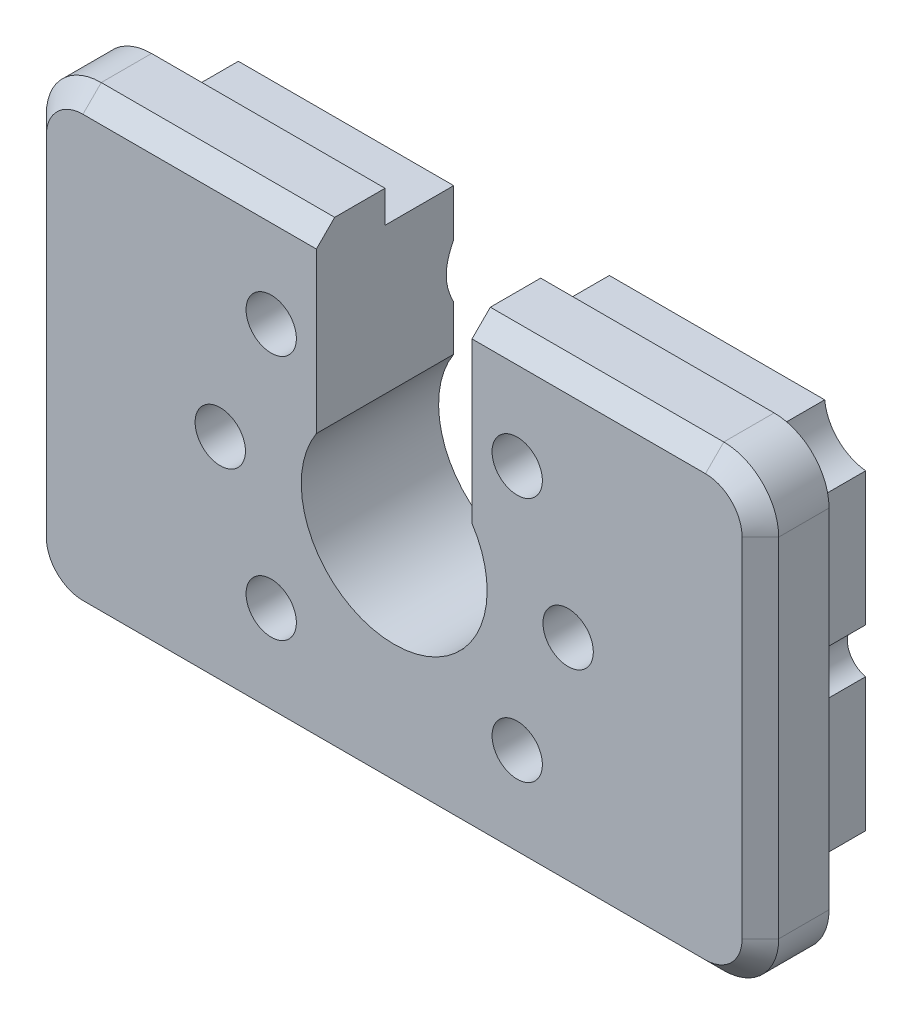
SolidWorks part; units mm, degrees
material "PET"
ref_plane "Front Plane" through (0, 0, 0) normal (0, 0, 1) x (1, 0, 0)
ref_plane "Top Plane" through (0, 0, 0) normal (0, 1, 0) x (1, 0, 0)
ref_plane "Right Plane" through (0, 0, 0) normal (1, 0, 0) x (0, 0, -1)
sketch "Sketch1" plane through (0, 0, 0) normal (0, 0, 1) x (1, 0, 0)
  line L1 (40, -25) -> (-40, -25)
  line L2 (40, -25) -> (40, 25)
  line L3 (40, 25) -> (-40, 25)
  line L4 (-40, -25) -> (-40, 25)
  line L5 (40, -25) -> (-40, 25) construction
  line L6 (40, 25) -> (-40, -25) construction
  point P0 (0, 0)
  dimension "D1" = 50
  dimension "D2" = 80
extrude "Boss-Extrude1" add sketch "Sketch1" against normal blind 7.5
sketch "Sketch2" plane through (0, 0, -7.5) normal (0, 0, -1) x (-1, 0, 0)
  line L8 (36.5, -21.5) -> (36.5, 21.5)
  line L9 (36.5, 21.5) -> (-36.5, 21.5)
  line L10 (-36.5, 21.5) -> (-36.5, -21.5)
  line L11 (-36.5, -21.5) -> (36.5, -21.5)
  line L12 (36.5, -21.5) -> (36.5, 21.5)
  line L13 (36.5, 21.5) -> (-36.5, 21.5)
  line L14 (-36.5, 21.5) -> (-36.5, -21.5)
  line L15 (-36.5, -21.5) -> (36.5, -21.5)
  dimension "D1" = 3.5
extrude "Boss-Extrude2" add sketch "Sketch2" along normal blind 7.5
sketch "Sketch3" plane through (0, 0, 0) normal (0, 0, 1) x (1, 0, 0)
  line L0 (0, 0) -> (0, 51.1675) construction
  line L1 (40, 25) -> (-40, 25) construction
  line L2 (8.5, 5.5473) -> (-8.5, 5.5473) construction
  line L3 (8.5, 5.5473) -> (8.5, 25)
  line L4 (8.5, 25) -> (-8.5, 25)
  line L5 (-8.5, 5.5473) -> (-8.5, 25)
  line L6 (8.5, 5.5473) -> (-8.5, 25) construction
  line L7 (8.5, 25) -> (-8.5, 5.5473) construction
  line L8 (0, 0) -> (-19, 0) construction
  arc A0 (-8.5, 5.5473) -> (8.5, 5.5473) centre (0, 0) ccw
  circle A1 centre (-19, 0) radius 2.75
  circle A2 centre (-13.435, 13.435) radius 2.75
  circle A3 centre (0, 19) radius 2.75 construction
  circle A4 centre (13.435, 13.435) radius 2.75
  circle A5 centre (19, 0) radius 2.75
  circle A6 centre (13.435, -13.435) radius 2.75
  circle A7 centre (0, -19) radius 2.75 construction
  circle A8 centre (-13.435, -13.435) radius 2.75
  point P3 (0, 15.2736)
  point P28 (0, 0)
  dimension "D4" = 5.5
  dimension "D2" = 17
  dimension "D3" = 19
  dimension "D5" = 8
extrude "Cut-Extrude1" cut sketch "Sketch3" against normal through all
fillet "Fillet1" radius 6 4 edges at (40, -25, -3.75) (-40, -25, -3.75) (-40, 25, -3.75) (40, 25, -3.75)
sketch "Sketch4" plane through (0, 0, -15) normal (0, 0, -1) x (-1, 0, 0)
  line L0 (-37, 22) -> (-37, -22) construction
  line L1 (-40, -19) -> (-40, 19) construction
  line L2 (-34, 25) -> (-8.5, 25) construction
  line L4 (34, -25) -> (-34, -25) construction
  line L5 (-37, -22) -> (0, -22) construction
  line L6 (0, 0) -> (0, -22) construction
  circle A0 centre (-37, 22) radius 5
  circle A1 centre (-37, -22) radius 5
  circle A2 centre (-37, 0) radius 2.5
  circle A3 centre (0, -22) radius 2.5
  circle A4 centre (37, -22) radius 5
  circle A5 centre (37, 0) radius 2.5
  circle A6 centre (37, 22) radius 5
  dimension "D4" = 5
  dimension "D5" = 10
  dimension "D1" = 3
  dimension "D2" = 3
  dimension "D3" = 3
extrude "Cut-Extrude2" cut sketch "Sketch4" against normal up to surface (7.5 mm away) up to face at (0, 5.8125, -7.5)
chamfer "Chamfer1" distance 2 angle 45 9 edges at (-21.25, 25, 0) (-38.2426, 23.2426, 0) (-40, 0, 0) (-38.2426, -23.2426, 0) (0, -25, 0) (38.2426, -23.2426, 0) (40, 0, 0) (38.2426, 23.2426, 0) (21.25, 25, 0)
chamfer "Chamfer2" distance 3 angle 45 6 edges at (16.185, -13.435, -15) (-16.25, 0, -15) (-10.685, -13.435, -15) (21.75, 0, -15) (16.185, 13.435, -15) (-10.685, 13.435, -15)
equation "\"hole_radius\"= 10.15mm"
equation "\"D1@Sketch3\"=\"hole_radius\"*2"
equation "\"M5_tap\"=4.2mm       ' Below you can do mesurements as follows: cm, mm, ft, in, m, "
equation "\"M5_clearence\"=5.5mm"
equation "\"M6_tap\"=5mm"
equation "\"M6_clearence\"=6.6mm"
equation "\"work_area_width\"=1100mm"
equation "\"work_area_depth\"=900mm"
equation "\"steel_base_width\"=80mm"
equation "\"steel_base_height\"=50mm"
equation "\"steel_base_wall_thickness\"=3mm"
equation "\"steel_base_radius\"=6mm"
equation "\"steel_sides_width\"=80mm    'this tube is rotated so flip width/height"
equation "\"steel_sides_height\"=50mm    'this tube is rotated so flip width/height"
equation "\"steel_sides_wall_thickness\"=3mm"
equation "\"steel_sides_radius\"=6mm"
equation "\"steel_gantry_width\"=80mm    'this tube is rotated so flip width/height"
equation "\"steel_gantry_height\"=50mm    'this tube is rotated so flip width/height"
equation "\"steel_gantry_wall_thickness\"=3mm"
equation "\"steel_gantry_radius\"=6mm"
equation "\"steel_rollers_width\"=80mm"
equation "\"steel_rollers_height\"=50mm    'keep as low as possible as this increases how big plastic parts are"
equation "\"steel_rollers_wall_thickness\"=3mm"
equation "\"steel_rollers_radius\"=6mm"
equation "\"steel_zbox_width\"=80mm     'if the gantry height (rotated) is too thick, a wider zbox is necessary"
equation "\"steel_zbox_height\"=50mm    'hole patteren changes as the zbox and gantry height (rotated) changes."
equation "\"steel_zbox_wall_thickness\"=3mm"
equation "\"steel_zbox_radius\"=6mm"
equation "\"D2@Sketch1\"=\"steel_zbox_width\""
equation "\"D1@Sketch1\"=\"steel_zbox_height\""
equation "\"D1@Sketch2\"=\"steel_zbox_wall_thickness\"+ 0.5mm"
equation "\"D1@Fillet1\"=\"steel_zbox_radius\""
